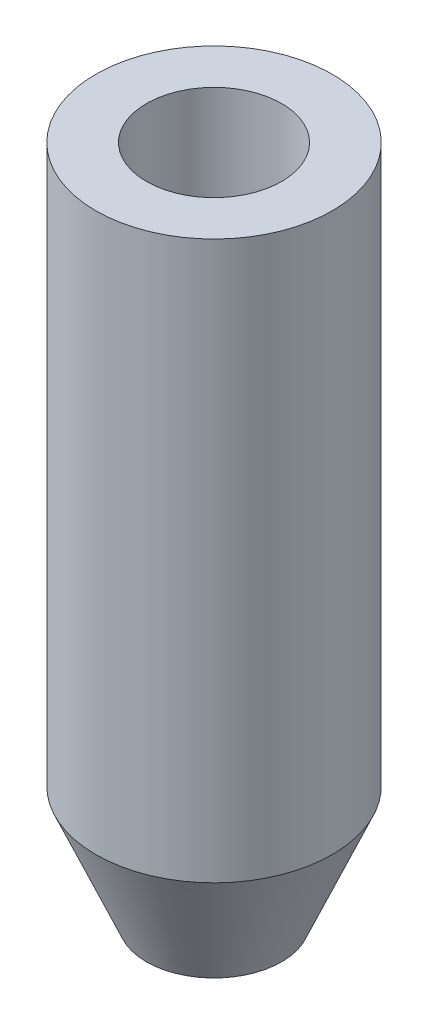
SolidWorks part; units mm, degrees
material "Copper"
ref_plane "Front Plane" through (0, 0, 0) normal (0, 0, 1) x (1, 0, 0)
ref_plane "Top Plane" through (0, 0, 0) normal (0, 1, 0) x (1, 0, 0)
ref_plane "Right Plane" through (0, 0, 0) normal (1, 0, 0) x (0, 0, -1)
sketch "Sketch1" plane through (0, 0, 0) normal (0, 1, 0) x (1, 0, 0)
  circle A0 centre (0, 0) radius 3.5
  dimension "D1" = 7
extrude "Boss-Extrude1" add sketch "Sketch1" along normal mid plane 20 contours A0
chamfer "Chamfer1" distance 1.5 distance2 3.5 1 edges at (0, -10, 3.5) first distance on face at (0, -10, 3.5)
sketch "Sketch2" plane through (0, -10, 0) normal (0, -1, 0) x (1, 0, 0)
  circle A0 centre (0, 0) radius 0.875
  dimension "D1" = 1.75
extrude "Cut-Extrude1" cut sketch "Sketch2" against normal through all both and the other way through all
sketch "Sketch3" plane through (0, -10, 0) normal (0, -1, 0) x (1, 0, 0)
  circle A0 centre (0, 0) radius 1.35
  dimension "D1" = 2.7
extrude "Cut-Extrude2" cut sketch "Sketch3" against normal blind 3.5
sketch "Sketch4" plane through (0, 10, 0) normal (0, 1, 0) x (1, 0, 0)
  circle A0 centre (0, 0) radius 2
  dimension "D1" = 4
extrude "Cut-Extrude3" cut sketch "Sketch4" against normal blind 5
